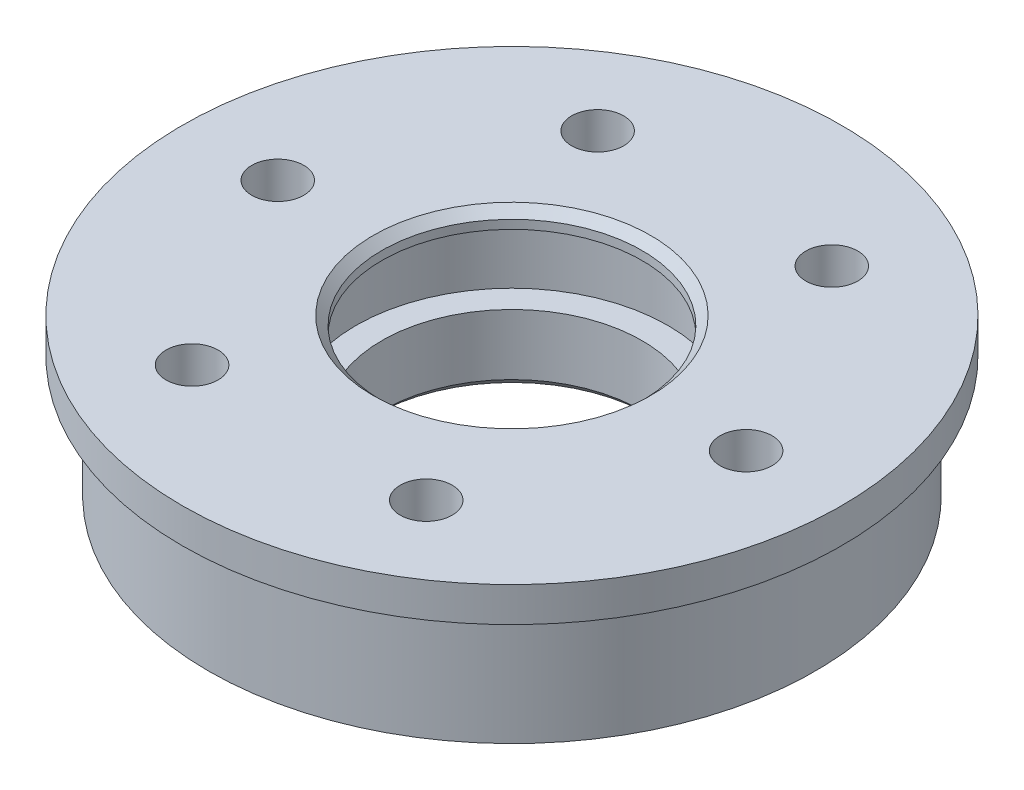
SolidWorks part; units mm, degrees
ref_plane "Front Plane" through (0, 0, 0) normal (0, 0, 1) x (1, 0, 0)
ref_plane "Top Plane" through (0, 0, 0) normal (0, 1, 0) x (1, 0, 0)
ref_plane "Right Plane" through (0, 0, 0) normal (1, 0, 0) x (0, 0, -1)
sketch "Sketch1" plane through (0, 0, 0) normal (0, 1, 0) x (1, 0, 0)
  circle A0 centre (0, 0) radius 13.5 construction
  circle A1 centre (13.5, 0) radius 1.5
  circle A2 centre (6.75, -11.6913) radius 1.5
  circle A3 centre (-6.75, -11.6913) radius 1.5
  circle A4 centre (-13.5, 0) radius 1.5
  circle A5 centre (-6.75, 11.6913) radius 1.5
  circle A6 centre (6.75, 11.6913) radius 1.5
  circle A7 centre (0, 0) radius 17.5
  circle A8 centre (0, 0) radius 7.5
  point P17 (0, 0)
  dimension "D1" = 27
  dimension "D2" = 3
  dimension "D4" = 35
  dimension "D5" = 15
  dimension "D3" = 6
extrude "Boss-Extrude1" add sketch "Sketch1" along normal mid plane 9
sketch "Sketch2" plane through (0, 0, 0) normal (0, 1, 0) x (1, 0, 0)
  circle A0 centre (0, 0) radius 9
  dimension "D1" = 18
extrude "Cut-Extrude1" cut sketch "Sketch2" along normal blind 4 from offset 0.5 offset against normal yes
sketch "Sketch3" plane through (0, -4.5, 0) normal (0, -1, 0) x (1, 0, 0)
  circle A0 centre (0, 0) radius 12
  circle A1 centre (0, 0) radius 15
  circle A2 centre (-13.5, 0) radius 1.5 construction
extrude "Boss-Extrude2" add sketch "Sketch3" against normal blind 1.5
chamfer "Chamfer1" distance 0.5 angle 45 2 edges at (0, -4.5, 7.5) (0, 4.5, 7.5)
sketch "Sketch4" plane through (0, 4.5, 0) normal (0, 1, 0) x (1, 0, 0)
  circle A0 centre (0, 0) radius 19
  circle A1 centre (0, 0) radius 17.5 construction
  circle A2 centre (0, 0) radius 17.5
  dimension "D1" = 1.5
extrude "Boss-Extrude3" add sketch "Sketch4" against normal blind 2
sketch "Sketch5" plane through (0, -4.5, 0) normal (0, -1, 0) x (-1, 0, 0)
  line L0 (0, 0) -> (-10.8253, -6.25) construction
  line L1 (0, 0) -> (-12.5, 0) construction
  circle A0 centre (0, 0) radius 12.5 construction
  circle A1 centre (-10.8253, -6.25) radius 2.35
  circle A2 centre (-10.8253, 6.25) radius 2.35
  circle A3 centre (0, 12.5) radius 2.35
  circle A4 centre (10.8253, 6.25) radius 2.35
  circle A5 centre (10.8253, -6.25) radius 2.35
  circle A6 centre (0, -12.5) radius 2.35
  point P7 (11.5669, -6.9612)
  point P8 (0, 0)
  point P18 (0, 0)
  dimension "D1" = 4.7
  dimension "D2" = 25
  dimension "D3" = 30
  dimension "D4" = 6
extrude "Cut-Extrude2" cut sketch "Sketch5" against normal blind 4
equation "\"D5@Sketch1\"=18-3"
